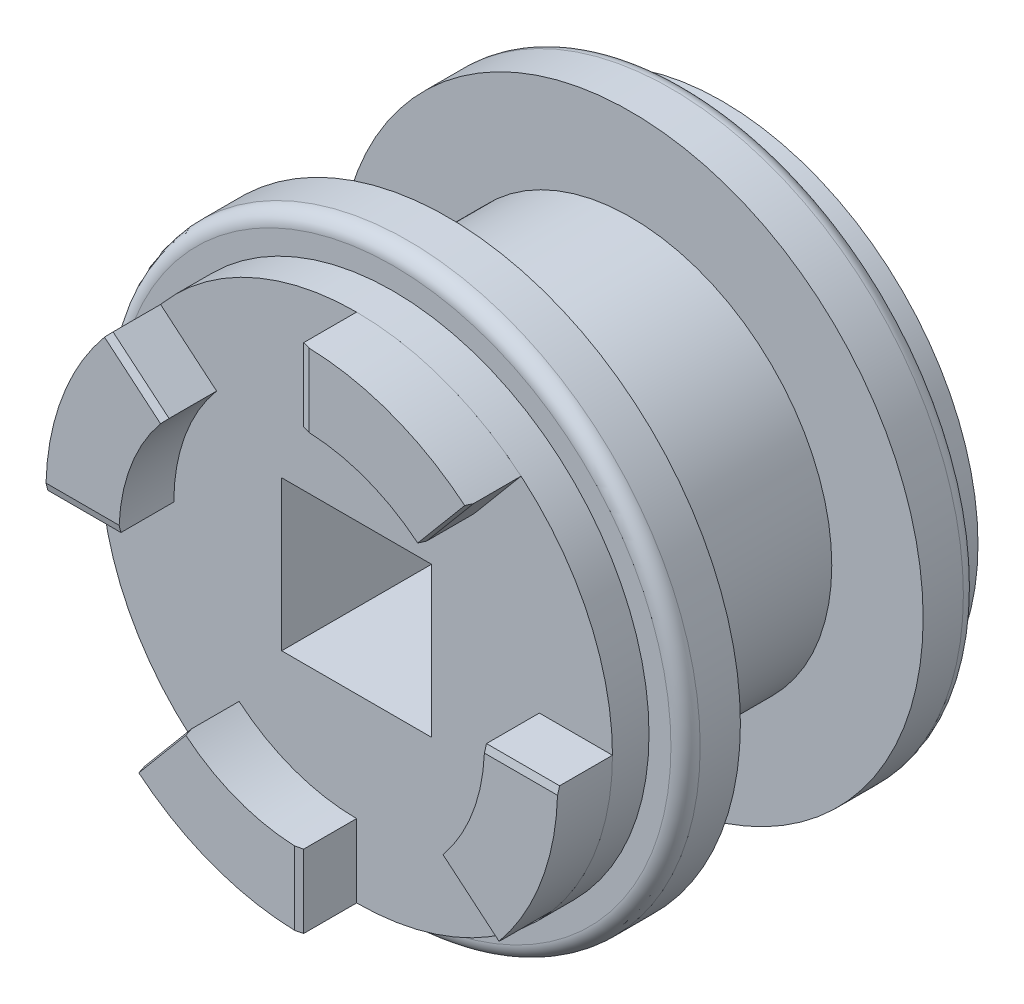
SolidWorks part; units mm, degrees
note: '?' marks a value the reader was unsure of. The reader was unsure of these and kept them because the rebuilt part matched: shared geometry of "Sketch12<2>", "Sketch11<3>".
ref_plane "Front Plane" through (0, 0, 0) normal (0, 0, 1) x (1, 0, 0)
ref_plane "Top Plane" through (0, 0, 0) normal (0, 1, 0) x (1, 0, 0)
ref_plane "Right Plane" through (0, 0, 0) normal (1, 0, 0) x (0, 0, -1)
sketch "Sketch1" plane through (0, 0, 0) normal (0, 0, 1) x (1, 0, 0)
  circle A0 centre (0, 0) radius 7
  dimension "D1" = 14
extrude "Boss-Extrude1" add sketch "Sketch1" along normal blind 10
sketch "Sketch2" plane through (0, 0, 10) normal (0, 0, 1) x (1, 0, 0)
  line L0 (0, 5) -> (0, 7)
  line L1 (3.2139, 3.8302) -> (4.4995, 5.3623)
  line L2 (0.6959, 4.9513) -> (0.9742, 6.9319)
  arc A0 (0, 7) -> (4.4995, 5.3623) centre (0, 0) cw
  circle A1 centre (0, 0) radius 7 construction
  arc A2 (0, 5) -> (3.2139, 3.8302) centre (0, 0) cw
  circle M5 centre (0, 0) radius 7
  dimension "D1" = 5
  dimension "D3" = 8
  dimension "D2" = 40
extrude "Boss-Extrude2" add sketch "Sketch2" along normal blind 1.5 separate body contours L0 A2 L2 M5 | L2 A2 L1 M5
ref_axis "Axis1" through (0, 0, 10) along (0, 0, -1)?
ref_plane "Plane1" through (0, 7, 0) normal (0, 1, 0) x (1, 0, 0)
sketch "Sketch10" plane through (0, 7, 0) normal (0, 1, 0) x (1, 0, 0)
  line L0 (0, -10) -> (4.4995, -10)
  line L1 (4.4995, -10) -> (4.4995, -11.5)
  line L2 (4.4995, -11.5) -> (3.2139, -11.5)
  line L3 (0, -10.7) -> (0, -10)
  line L4 (0, -10.7) -> (3.2139, -11.5)
  line L5 (4.4995, -10) -> (0, -10) construction
  dimension "D1" = 0.8
wrap "Wrap1" [suppressed] sketch "Sketch10" source sketch "Sketch10" thickness 3 parameters "D1"=3
chamfer "Chamfer2" distance 0.2 angle 15 2 edges at (3.8567, 4.5963, 11.5) (0, 6, 11.5)
fillet "Fillet1" [suppressed] radius 0.2
pattern_circular "CirPattern1" count 4 over 360 about axis through (0, 0, 0) along (0, 0, 1) of bodies 102
sketch "Sketch11" plane through (0, 0, 0) normal (0, 0, -1) x (-1, 0, 0)
  line L1 (2.05, -2.05) -> (-2.05, -2.05)
  line L2 (2.05, -2.05) -> (2.05, 2.05)
  line L3 (2.05, 2.05) -> (-2.05, 2.05)
  line L4 (-2.05, -2.05) -> (-2.05, 2.05)
  line L5 (2.05, -2.05) -> (-2.05, 2.05) construction
  line L6 (2.05, 2.05) -> (-2.05, -2.05) construction
  circle A0 centre (0, 0) radius 3.7
  point P0 (0, 0)
  dimension "D2" = 7.4
  dimension "D1" = 4.1
extrude "Cut-Extrude1" cut sketch "Sketch11" against normal up to next (10 mm away) contours L4 L1 L2 L3
ref_plane "Plane2" through (0, 0, 5) normal (0, 0, 1) x (1, 0, 0)
sketch "Sketch12" plane through (0, 0, 5) normal (0, 0, 1) x (1, 0, 0)
  circle A0 centre (0, 0) radius 8
  circle A1 centre (0, 0) radius 7
  dimension "D1" = 16
  dimension "D2" = 14
extrude "Boss-Extrude3" add sketch "Sketch12" along normal mid plane 8
extrude "Cut-Extrude-Thin1" cut sketch "Sketch12<2>" against normal mid plane 5 thin contours A0
sketch "Sketch12<2>" plane through (0, 0, 5) normal (0, 0, 1) x (1, 0, 0) same geometry as "Sketch12"
fillet "Fillet3" radius 0.4 2 edges at (8, 0, 1) (8, 0, 9)
extrude "Cut-Extrude2" cut sketch "Sketch11<3>" against normal blind 2 contours A0 L1 L4 L3 L2
sketch "Sketch11<3>" plane through (0, 0, 0) normal (0, 0, -1) x (-1, 0, 0) same geometry as "Sketch11"
